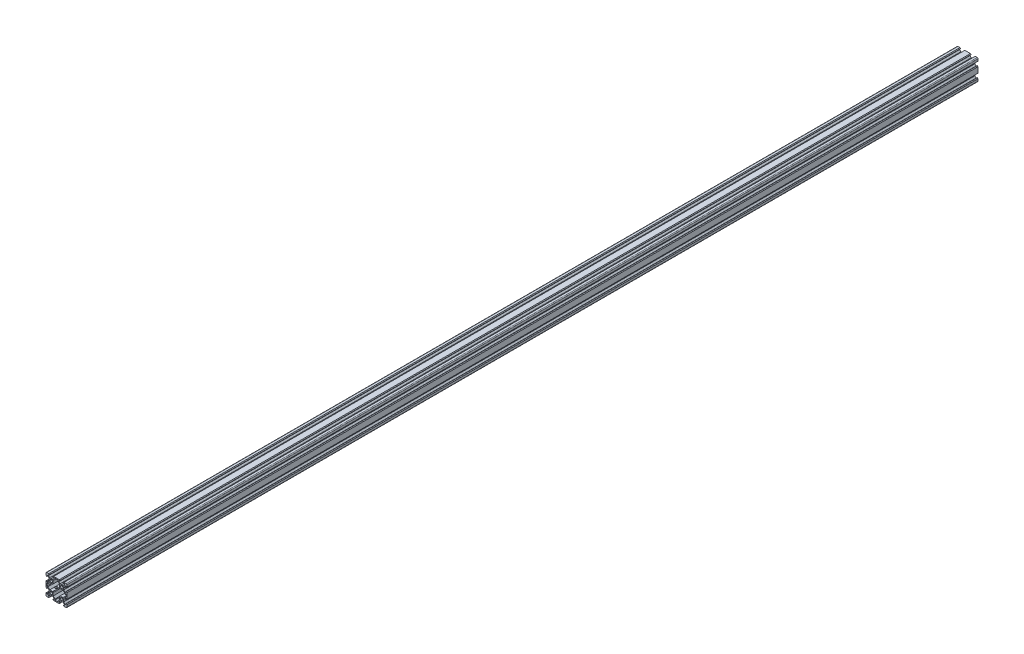
SolidWorks part; units mm, degrees
material "6061-T6 (SS)"
ref_plane "Front Plane" through (0, 0, 0) normal (0, 0, 1) x (1, 0, 0)
ref_plane "Top Plane" through (0, 0, 0) normal (0, 1, 0) x (1, 0, 0)
ref_plane "Right Plane" through (0, 0, 0) normal (1, 0, 0) x (0, 0, -1)
sketch "Sketch1" plane through (0, 0, 0) normal (0, 0, 1) x (1, 0, 0)
  line L1 (18.5, -20) -> (-18.5, -20)
  line L2 (20, -18.5) -> (20, 18.5)
  line L3 (18.5, 20) -> (-18.5, 20)
  line L4 (-20, -18.5) -> (-20, 18.5)
  line L5 (20, -20) -> (-20, 20) construction
  line L6 (20, 20) -> (-20, -20) construction
  circle A0 centre (-10, 10) radius 2.3
  circle A1 centre (10, -10) radius 2.3
  circle A2 centre (10, 10) radius 2.3
  circle A3 centre (-10, -10) radius 2.3
  arc A4 (-18.5, -20) -> (-20, -18.5) centre (-18.5, -18.5) cw
  arc A5 (18.5, -20) -> (20, -18.5) centre (18.5, -18.5) ccw
  arc A6 (20, 18.5) -> (18.5, 20) centre (18.5, 18.5) ccw
  arc A7 (-18.5, 20) -> (-20, 18.5) centre (-18.5, 18.5) ccw
  point P0 (0, 0)
  line B0 (-10, 10) -> (-10, 20) construction
  line B1 (-10, 13.69) -> (-10.21, 13.9)
  line B2 (-10.21, 13.9) -> (-12.8393, 13.9)
  line B3 (-12.8393, 13.9) -> (-15.5, 16.5607)
  line B4 (-15.5, 16.5607) -> (-15.5, 18.2)
  line B5 (-15.5, 18.2) -> (-13.395, 18.2)
  line B6 (-13.395, 18.2) -> (-13.395, 18.815)
  line B7 (-13.395, 18.815) -> (-14.58, 20)
  line B8 (-14.58, 20) -> (-5.42, 20)
  line B9 (-10, 10) -> (-15.9132, 15.9132) construction
  line B10 (-6.605, 18.815) -> (-5.42, 20)
  line B11 (-6.605, 18.2) -> (-6.605, 18.815)
  line B12 (-4.5, 18.2) -> (-6.605, 18.2)
  line B13 (-4.5, 16.5607) -> (-4.5, 18.2)
  line B14 (-7.1607, 13.9) -> (-4.5, 16.5607)
  line B15 (-9.79, 13.9) -> (-7.1607, 13.9)
  line B16 (-10, 13.69) -> (-9.79, 13.9)
  line B17 (10, 10) -> (10, 20) construction
  line B18 (10, 13.69) -> (9.79, 13.9)
  line B19 (9.79, 13.9) -> (7.1607, 13.9)
  line B20 (7.1607, 13.9) -> (4.5, 16.5607)
  line B21 (4.5, 16.5607) -> (4.5, 18.2)
  line B22 (4.5, 18.2) -> (6.605, 18.2)
  line B23 (6.605, 18.2) -> (6.605, 18.815)
  line B24 (6.605, 18.815) -> (5.42, 20)
  line B25 (5.42, 20) -> (14.58, 20)
  line B26 (10, 10) -> (4.0868, 15.9132) construction
  line B27 (13.395, 18.815) -> (14.58, 20)
  line B28 (13.395, 18.2) -> (13.395, 18.815)
  line B29 (15.5, 18.2) -> (13.395, 18.2)
  line B30 (15.5, 16.5607) -> (15.5, 18.2)
  line B31 (12.8393, 13.9) -> (15.5, 16.5607)
  line B32 (10.21, 13.9) -> (12.8393, 13.9)
  line B33 (10, 13.69) -> (10.21, 13.9)
  line B34 (-10, 10) -> (-20, 10) construction
  line B35 (-13.69, 10) -> (-13.9, 9.79)
  line B36 (-13.9, 9.79) -> (-13.9, 7.1607)
  line B37 (-13.9, 7.1607) -> (-16.5607, 4.5)
  line B38 (-16.5607, 4.5) -> (-18.2, 4.5)
  line B39 (-18.2, 4.5) -> (-18.2, 6.605)
  line B40 (-18.2, 6.605) -> (-18.815, 6.605)
  line B41 (-18.815, 6.605) -> (-20, 5.42)
  line B42 (-20, 5.42) -> (-20, 14.58)
  line B43 (-10, 10) -> (-15.9132, 4.0868) construction
  line B44 (-18.815, 13.395) -> (-20, 14.58)
  line B45 (-18.2, 13.395) -> (-18.815, 13.395)
  line B46 (-18.2, 15.5) -> (-18.2, 13.395)
  line B47 (-16.5607, 15.5) -> (-18.2, 15.5)
  line B48 (-13.9, 12.8393) -> (-16.5607, 15.5)
  line B49 (-13.9, 10.21) -> (-13.9, 12.8393)
  line B50 (-13.69, 10) -> (-13.9, 10.21)
  line B51 (-10, -10) -> (-20, -10) construction
  line B52 (-13.69, -10) -> (-13.9, -10.21)
  line B53 (-13.9, -10.21) -> (-13.9, -12.8393)
  line B54 (-13.9, -12.8393) -> (-16.5607, -15.5)
  line B55 (-16.5607, -15.5) -> (-18.2, -15.5)
  line B56 (-18.2, -15.5) -> (-18.2, -13.395)
  line B57 (-18.2, -13.395) -> (-18.815, -13.395)
  line B58 (-18.815, -13.395) -> (-20, -14.58)
  line B59 (-20, -14.58) -> (-20, -5.42)
  line B60 (-10, -10) -> (-15.9132, -15.9132) construction
  line B61 (-18.815, -6.605) -> (-20, -5.42)
  line B62 (-18.2, -6.605) -> (-18.815, -6.605)
  line B63 (-18.2, -4.5) -> (-18.2, -6.605)
  line B64 (-16.5607, -4.5) -> (-18.2, -4.5)
  line B65 (-13.9, -7.1607) -> (-16.5607, -4.5)
  line B66 (-13.9, -9.79) -> (-13.9, -7.1607)
  line B67 (-13.69, -10) -> (-13.9, -9.79)
  line B68 (-10, -10) -> (-10, -20) construction
  line B69 (-10, -13.69) -> (-9.79, -13.9)
  line B70 (-9.79, -13.9) -> (-7.1607, -13.9)
  line B71 (-7.1607, -13.9) -> (-4.5, -16.5607)
  line B72 (-4.5, -16.5607) -> (-4.5, -18.2)
  line B73 (-4.5, -18.2) -> (-6.605, -18.2)
  line B74 (-6.605, -18.2) -> (-6.605, -18.815)
  line B75 (-6.605, -18.815) -> (-5.42, -20)
  line B76 (-5.42, -20) -> (-14.58, -20)
  line B77 (-10, -10) -> (-4.0868, -15.9132) construction
  line B78 (-13.395, -18.815) -> (-14.58, -20)
  line B79 (-13.395, -18.2) -> (-13.395, -18.815)
  line B80 (-15.5, -18.2) -> (-13.395, -18.2)
  line B81 (-15.5, -16.5607) -> (-15.5, -18.2)
  line B82 (-12.8393, -13.9) -> (-15.5, -16.5607)
  line B83 (-10.21, -13.9) -> (-12.8393, -13.9)
  line B84 (-10, -13.69) -> (-10.21, -13.9)
  line B85 (10, -10) -> (10, -20) construction
  line B86 (10, -13.69) -> (10.21, -13.9)
  line B87 (10.21, -13.9) -> (12.8393, -13.9)
  line B88 (12.8393, -13.9) -> (15.5, -16.5607)
  line B89 (15.5, -16.5607) -> (15.5, -18.2)
  line B90 (15.5, -18.2) -> (13.395, -18.2)
  line B91 (13.395, -18.2) -> (13.395, -18.815)
  line B92 (13.395, -18.815) -> (14.58, -20)
  line B93 (14.58, -20) -> (5.42, -20)
  line B94 (10, -10) -> (15.9132, -15.9132) construction
  line B95 (6.605, -18.815) -> (5.42, -20)
  line B96 (6.605, -18.2) -> (6.605, -18.815)
  line B97 (4.5, -18.2) -> (6.605, -18.2)
  line B98 (4.5, -16.5607) -> (4.5, -18.2)
  line B99 (7.1607, -13.9) -> (4.5, -16.5607)
  line B100 (9.79, -13.9) -> (7.1607, -13.9)
  line B101 (10, -13.69) -> (9.79, -13.9)
  line B102 (10, 10) -> (20, 10) construction
  line B103 (13.69, 10) -> (13.9, 10.21)
  line B104 (13.9, 10.21) -> (13.9, 12.8393)
  line B105 (13.9, 12.8393) -> (16.5607, 15.5)
  line B106 (16.5607, 15.5) -> (18.2, 15.5)
  line B107 (18.2, 15.5) -> (18.2, 13.395)
  line B108 (18.2, 13.395) -> (18.815, 13.395)
  line B109 (18.815, 13.395) -> (20, 14.58)
  line B110 (20, 14.58) -> (20, 5.42)
  line B111 (10, 10) -> (15.9132, 15.9132) construction
  line B112 (18.815, 6.605) -> (20, 5.42)
  line B113 (18.2, 6.605) -> (18.815, 6.605)
  line B114 (18.2, 4.5) -> (18.2, 6.605)
  line B115 (16.5607, 4.5) -> (18.2, 4.5)
  line B116 (13.9, 7.1607) -> (16.5607, 4.5)
  line B117 (13.9, 9.79) -> (13.9, 7.1607)
  line B118 (13.69, 10) -> (13.9, 9.79)
  line B119 (10, -10) -> (20, -10) construction
  line B120 (13.69, -10) -> (13.9, -9.79)
  line B121 (13.9, -9.79) -> (13.9, -7.1607)
  line B122 (13.9, -7.1607) -> (16.5607, -4.5)
  line B123 (16.5607, -4.5) -> (18.2, -4.5)
  line B124 (18.2, -4.5) -> (18.2, -6.605)
  line B125 (18.2, -6.605) -> (18.815, -6.605)
  line B126 (18.815, -6.605) -> (20, -5.42)
  line B127 (20, -5.42) -> (20, -14.58)
  line B128 (10, -10) -> (15.9132, -4.0868) construction
  line B129 (18.815, -13.395) -> (20, -14.58)
  line B130 (18.2, -13.395) -> (18.815, -13.395)
  line B131 (18.2, -15.5) -> (18.2, -13.395)
  line B132 (16.5607, -15.5) -> (18.2, -15.5)
  line B133 (13.9, -12.8393) -> (16.5607, -15.5)
  line B134 (13.9, -10.21) -> (13.9, -12.8393)
  line B135 (13.69, -10) -> (13.9, -10.21)
  line B136 (-18.2, -2.7) -> (-18.2, 2.7)
  line B137 (-18.2, 2.7) -> (-16.2393, 2.7)
  line B138 (-16.2393, 2.7) -> (-12.8393, 6.1)
  line B139 (-12.8393, 6.1) -> (-7.1607, 6.1)
  line B140 (-10, 6.1) -> (-10, 0) construction
  line B141 (-10, 0) -> (-18.2, 0) construction
  line B142 (-12.8393, -6.1) -> (-7.1607, -6.1)
  line B143 (-16.2393, -2.7) -> (-12.8393, -6.1)
  line B144 (-18.2, -2.7) -> (-16.2393, -2.7)
  line B145 (-10, 6.1) -> (-10, 10) construction
  line B146 (-10, 10) -> (-15.0927, 4.9073) construction
  line B147 (-10, 10) -> (-6.3747, 6.3747) construction
  line B148 (2.7, 18.2) -> (2.7, 16.2393)
  line B149 (2.7, 16.2393) -> (6.1, 12.8393)
  line B150 (6.1, 12.8393) -> (6.1, 7.1607)
  line B151 (-6.1, 12.8393) -> (-6.1, 7.1607)
  line B152 (-2.7, 16.2393) -> (-6.1, 12.8393)
  line B153 (-2.7, 18.2) -> (-2.7, 16.2393)
  line B154 (2.7, 18.2) -> (-2.7, 18.2)
  line B155 (2.7, -18.2) -> (-2.7, -18.2)
  line B156 (-2.7, -18.2) -> (-2.7, -16.2393)
  line B157 (-2.7, -16.2393) -> (-6.1, -12.8393)
  line B158 (-6.1, -12.8393) -> (-6.1, -7.1607)
  line B159 (6.1, -12.8393) -> (6.1, -7.1607)
  line B160 (2.7, -16.2393) -> (6.1, -12.8393)
  line B161 (2.7, -18.2) -> (2.7, -16.2393)
  line B162 (0, 18.2) -> (0, -18.2) construction
  line B163 (12.8393, -6.1) -> (7.1607, -6.1)
  line B164 (16.2393, -2.7) -> (12.8393, -6.1)
  line B165 (18.2, -2.7) -> (16.2393, -2.7)
  line B166 (18.2, -2.7) -> (18.2, 2.7)
  line B167 (18.2, 2.7) -> (16.2393, 2.7)
  line B168 (16.2393, 2.7) -> (12.8393, 6.1)
  line B169 (12.8393, 6.1) -> (7.1607, 6.1)
  line B170 (-7.1607, 6.1) -> (-6.1, 7.1607)
  line B171 (6.1, 7.1607) -> (7.1607, 6.1)
  line B172 (7.1607, -6.1) -> (6.1, -7.1607)
  line B173 (-6.1, -7.1607) -> (-7.1607, -6.1)
  dimension "D4" = 4.6
  dimension "D5" = 1.5
  dimension "D1" = 40
  dimension "D2" = 10
  dimension "D3" = 10
sketch_block_instance "V Slot 2-1"
sketch_block "V Slot 2" parameters "D1"=10, "D2"=11, "D3"=4.3, "D4"=1.8, "D5"=0.21, "D6"=45, "D7"=9.16, "D8"=1.5, "D9"=6.79
sketch_block_instance "V Slot 2-2"
sketch_block_instance "V Slot 2-3"
sketch_block_instance "V Slot 2-4"
sketch_block_instance "V Slot 2-5"
sketch_block_instance "V Slot 2-6"
sketch_block_instance "V Slot 2-7"
sketch_block_instance "V Slot 2-8"
sketch_block_instance "Center Cutout 2-1"
sketch_block "Center Cutout 2" parameters "D1"=5.4, "D2"=12.2, "D3"=8.2, "D4"=45, "D5"=10, "D6"=1.5
extrude "Boss-Extrude1" add sketch "Sketch1" along normal blind 1750 contours B135 B120 B121 B122 B123 B124 B125 B126 L2 B112 B113 B114 B115 B116 B117 B118 B103 B104 B105 B106 B107 B108 B109 A6 L3 B27 B28 B29 B30 B31 B32 B33 B18 B19 B20 B21 B22 B23 B24 B10 B11 B12 B13 B14 B15 B16 B1 B2 B3 region at (16.54, -19.4343, 0)
sketch "Sketch2" plane through (0, 20, 0) normal (0, 1, 0) x (1, 0, 0)
  line L0 (-9.79, -1750) -> (-7.1607, -1750) construction
  line L1 (-20, -1750) -> (-20, 0) construction
  line L2 (10.21, -1750) -> (12.8393, -1750) construction
  line L3 (20, -1750) -> (20, 0) construction
  line L4 (9.79, 0) -> (7.1607, 0) construction
  circle A0 centre (-10, -1740) radius 2.6
  circle A1 centre (10, -1740) radius 2.6
  circle A2 centre (-10, -10) radius 2.6
  circle A3 centre (10, -10) radius 2.6
  dimension "D1" = 5.2
  dimension "D2" = 5.2
  dimension "D7" = 5.2
  dimension "D8" = 5.2
  dimension "D3" = 10
  dimension "D4" = 10
  dimension "D5" = 10
  dimension "D6" = 10
  dimension "D9" = 10
  dimension "D10" = 10
  dimension "D11" = 10
  dimension "D12" = 10
extrude "Cut-Extrude1" cut sketch "Sketch2" against normal through all
sketch "Sketch3" plane through (20, 0, 0) normal (1, 0, 0) x (0, 0, -1)
  line L0 (-1750, 20) -> (0, 20) construction
  line L1 (0, 10.21) -> (0, 12.8393) construction
  line L2 (0, -10.21) -> (0, -12.8393) construction
  line L3 (-1750, -20) -> (0, -20) construction
  line L4 (-1750, -5.42) -> (-1750, 5.42) construction
  line L5 (-1750, 10.21) -> (-1750, 12.8393) construction
  circle A0 centre (-30, 10) radius 2.6
  circle A1 centre (-30, -10) radius 2.6
  circle A2 centre (-1720, 10) radius 2.6
  circle A3 centre (-1720, -10) radius 2.6
  dimension "D1" = 5.2
  dimension "D2" = 5.2
  dimension "D7" = 5.2
  dimension "D8" = 5.2
  dimension "D3" = 10
  dimension "D4" = 30
  dimension "D5" = 30
  dimension "D6" = 10
  dimension "D9" = 30
  dimension "D10" = 30
  dimension "D11" = 10
  dimension "D12" = 10
extrude "Cut-Extrude2" cut sketch "Sketch3" against normal through all
sketch "Sketch4" plane through (0, 20, 0) normal (0, 1, 0) x (1, 0, 0)
  line L0 (-20, -875) -> (20, -875) construction
  line L1 (-20, -1750) -> (-20, 0) construction
  line L2 (20, -1750) -> (20, 0) construction
  line L3 (5.42, -1750) -> (-5.42, -1750) construction
  circle A0 centre (-10, -885) radius 2.6
  circle A1 centre (10, -885) radius 2.6
  dimension "D2" = 5.2
  dimension "D3" = 5.2
  dimension "D1" = 875
  dimension "D4" = 10
  dimension "D5" = 10
  dimension "D6" = 10
  dimension "D7" = 10
extrude "Cut-Extrude3" cut sketch "Sketch4" against normal through all
sketch "Sketch5" plane through (20, 0, 0) normal (1, 0, 0) x (0, 0, -1)
  line L0 (-875, 20) -> (-875, -20) construction
  line L1 (-1750, 20) -> (0, 20) construction
  line L2 (-1750, -20) -> (0, -20) construction
  circle A0 centre (-865, 10) radius 2.6
  circle A1 centre (-865, -10) radius 2.6
  dimension "D2" = 5.2
  dimension "D3" = 5.2
  dimension "D1" = 875
  dimension "D4" = 10
  dimension "D5" = 10
  dimension "D6" = 10
  dimension "D7" = 10
extrude "Cut-Extrude4" cut sketch "Sketch5" against normal through all
